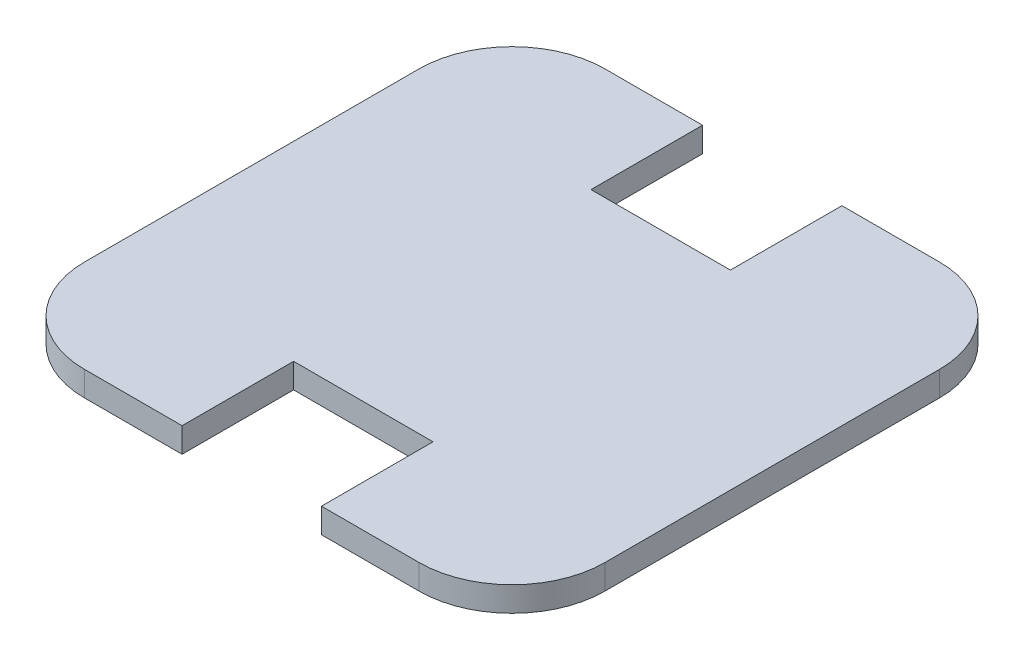
SolidWorks part; units mm, degrees
ref_plane "Front Plane" through (0, 0, 0) normal (0, 0, 1) x (1, 0, 0)
ref_plane "Top Plane" through (0, 0, 0) normal (0, 1, 0) x (1, 0, 0)
ref_plane "Right Plane" through (0, 0, 0) normal (1, 0, 0) x (0, 0, -1)
sketch "Layer1" plane through (0, 0, 0) normal (0, 1, 0) x (1, 0, 0)
  line L0 (11.25, 42) -> (27, 42)
  line L1 (-27, -42) -> (-11.25, -42)
  line L2 (-42, -27) -> (-42, 27)
  line L3 (-27, 42) -> (-11.25, 42)
  line L4 (42, -27) -> (42, 27)
  line L5 (-42, -42) -> (42, 42) construction
  line L6 (-42, 42) -> (42, -42) construction
  line L8 (-11.25, 42) -> (-11.25, 24)
  line L9 (-11.25, 24) -> (11.25, 24)
  line L10 (11.25, 42) -> (11.25, 24)
  line L12 (-11.25, -42) -> (-11.25, -24)
  line L13 (-11.25, -24) -> (11.25, -24)
  line L14 (11.25, -42) -> (11.25, -24)
  line L15 (11.25, -42) -> (27, -42)
  line L18 (-42, -21.5) -> (-42, 21.5)
  arc A0 (27, -42) -> (42, -27) centre (27, -27) ccw
  arc A1 (27, 42) -> (42, 27) centre (27, 27) cw
  arc A2 (-27, -42) -> (-42, -27) centre (-27, -27) cw
  arc A3 (-42, 27) -> (-27, 42) centre (-27, 27) cw
  point P0 (0, 0)
  point P30 (21.7219, 0)
  dimension "D9" = 15
  dimension "D1" = 84
  dimension "D2" = 84
  dimension "D3" = 18
  dimension "D4" = 22.5
  dimension "D5" = 18
  dimension "D6" = 22.5
  dimension "D7" = 30.75
  dimension "D8" = 30.75
  dimension "D10" = 43
extrude "Boss-Extrude1" add sketch "Layer1" along normal blind 4 contours A3 L2 A2 L1 L12 L13 L14 L15 A0 L4 A1 L0 L10 L9 L8 L3 | L2 region at (0, 0, 0)
sketch "Sketch4" plane through (0, 4, 0) normal (0, 1, 0) x (1, 0, 0)
  line L0 (11.25, 42) -> (27, 42) construction
  line L1 (20.125, -26.5) -> (33.125, -26.5)
  line L2 (20.125, -26.5) -> (20.125, 26.5)
  line L3 (20.125, 26.5) -> (33.125, 26.5)
  line L4 (33.125, -26.5) -> (33.125, 26.5)
  line L5 (20.125, -26.5) -> (33.125, 26.5) construction
  line L6 (20.125, 26.5) -> (33.125, -26.5) construction
  line L7 (42, -27) -> (42, 27) construction
  line L8 (-42, -27) -> (-42, 27) construction
  line L9 (-42, 21.5) -> (1, 21.5)
  line L10 (-42, 21.5) -> (-42, -21.5)
  line L11 (-42, -21.5) -> (1, -21.5)
  line L12 (1, 21.5) -> (1, -21.5)
  line L13 (-27, 42) -> (-11.25, 42) construction
  circle A0 centre (-32, 32) radius 5
  circle A1 centre (32, 32) radius 5
  circle A2 centre (32, -32) radius 5
  circle A3 centre (-32, -32) radius 5
  point P0 (26.625, 0)
  dimension "D9" = 10
  dimension "D1" = 53
  dimension "D2" = 13
  dimension "D3" = 15.5
  dimension "D4" = 8.875
  dimension "D5" = 43
  dimension "D6" = 43
  dimension "D7" = 0
  dimension "D8" = 20.5
  dimension "D10" = 10
  dimension "D11" = 10
  dimension "D12" = 2
  dimension "D13" = 2
equation "\"D6@Layer1\"=\"D4@Layer1\""
equation "\"D5@Layer1\"=\"D3@Layer1\""
equation "\"D2@Layer1\"=\"D1@Layer1\""
equation "\"D7@Layer1\"=(\"D2@Layer1\"-\"D4@Layer1\")/2"
equation "\"D8@Layer1\"=\"D7@Layer1\""
equation "\"D3@Sketch4\"=(\"D1@Layer1\"-\"D1@Sketch4\")/2"
equation "\"D4@Sketch4\"=(\"D7@Layer1\"-\"D2@Sketch4\")/2"
equation "\"D6@Sketch4\"=\"D5@Sketch4\""
equation "\"D8@Sketch4\"=(\"D1@Layer1\"-\"D5@Sketch4\")/2"
equation "\"D11@Sketch4\"=\"D10@Sketch4\""
